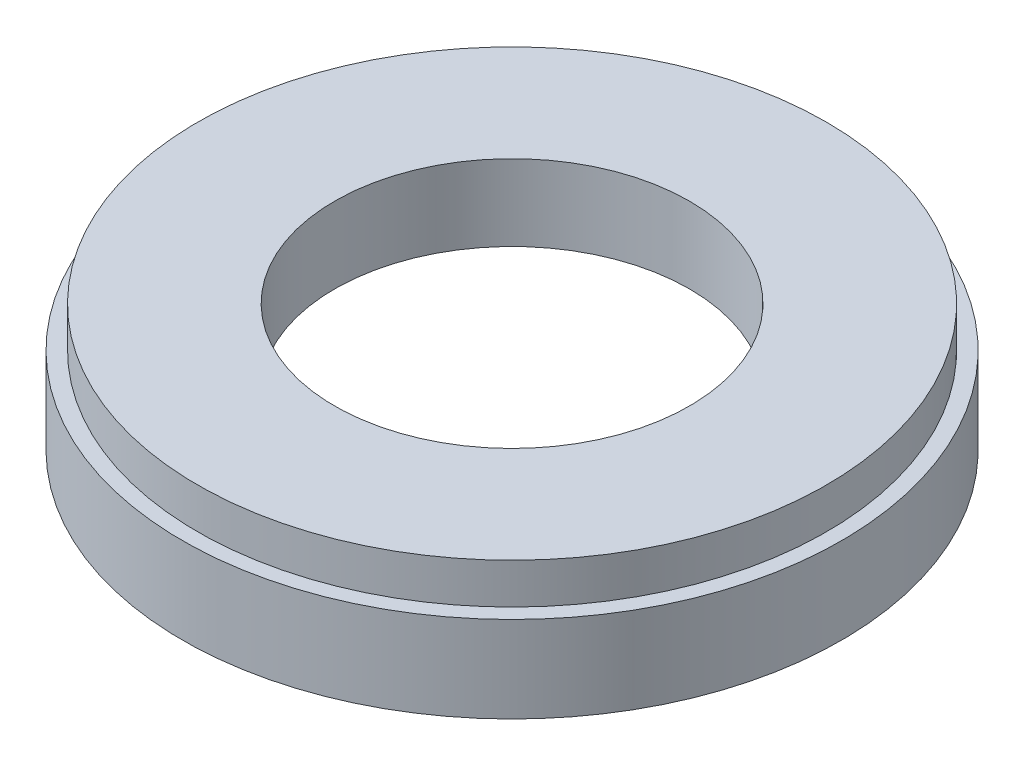
SolidWorks part; units mm, degrees
material "HYPALON"
ref_plane "Front Plane" through (0, 0, 0) normal (0, 0, 1) x (1, 0, 0)
ref_plane "Top Plane" through (0, 0, 0) normal (0, 1, 0) x (1, 0, 0)
ref_plane "Right Plane" through (0, 0, 0) normal (1, 0, 0) x (0, 0, -1)
sketch "Szkic1" plane through (0, 0, 0) normal (0, 0, 1) x (1, 0, 0)
  line L0 (0, 0) -> (-65, 0)
  line L1 (-65, 0) -> (-65, 15)
  line L2 (-65, 15) -> (-35, 15)
  line L3 (-35, 15) -> (-35, 0)
  line L4 (0, 0) -> (0, 23.5461)
  line L6 (-65, 0) -> (-63, 0)
  line L7 (-65, 0) -> (-65, -10)
  line L8 (-65, -10) -> (-63, -10)
  line L9 (-63, 0) -> (-63, -10)
  line L10 (-65, 15) -> (-62, 15)
  line L11 (-65, 15) -> (-65, 7)
  line L12 (-65, 7) -> (-62, 7)
  line L13 (-62, 15) -> (-62, 7)
  dimension "D1" = 65
  dimension "D2" = 15
  dimension "D3" = 35
  dimension "D4" = 3
  dimension "D5" = 8
  dimension "D6" = 10
  dimension "D7" = 2
revolve "Obrót1" add sketch "Szkic1" angle 360 about L4 region at (-49.2394, 7.3028, 0)
